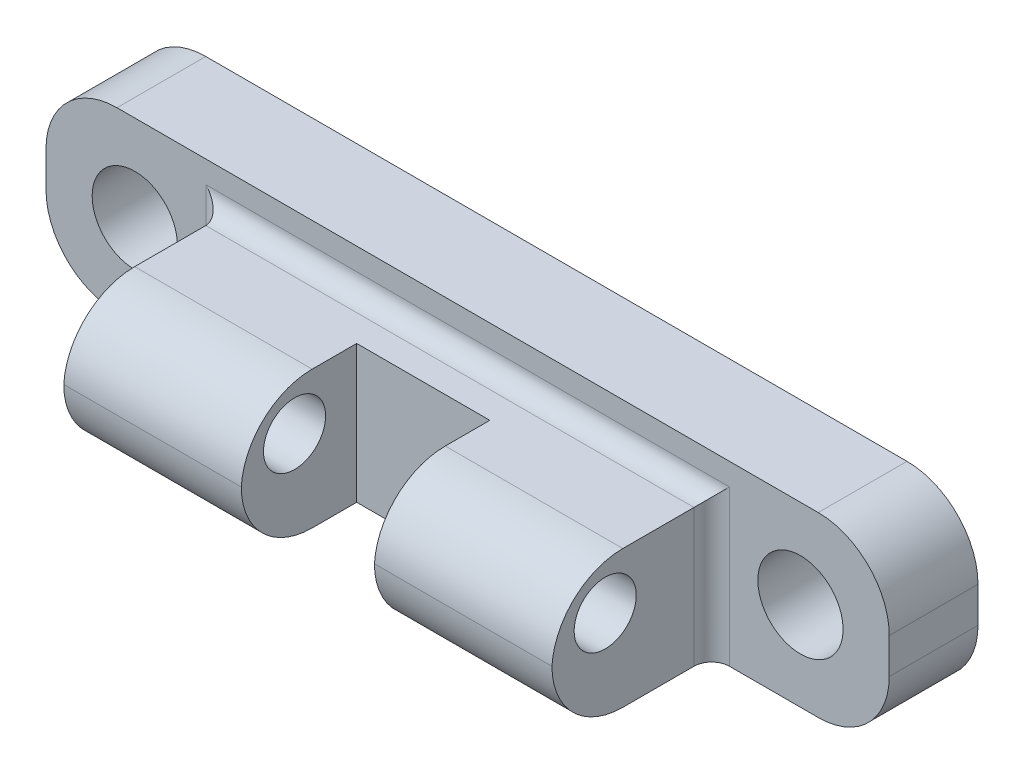
SolidWorks part; units mm, degrees
ref_plane "Front Plane" through (0, 0, 0) normal (0, 0, 1) x (1, 0, 0)
ref_plane "Top Plane" through (0, 0, 0) normal (0, 1, 0) x (1, 0, 0)
ref_plane "Right Plane" through (0, 0, 0) normal (1, 0, 0) x (0, 0, -1)
sketch "Sketch1" plane through (0, 0, 0) normal (0, 1, 0) x (1, 0, 0)
  line L3 (27.5, -2.7064) -> (17.5, -2.7064)
  line L4 (17.5, -2.7064) -> (17.5, 3.7936)
  line L5 (17.5, 3.7936) -> (10, 3.7936)
  line L6 (10, 3.7936) -> (10, -2.7064)
  line L7 (10, -2.7064) -> (0, -2.7064)
  line L8 (0, -2.7064) -> (0, 0)
  line L14 (-10, 11.2936) -> (-10, 6.2936)
  line L15 (-10, 6.2936) -> (0, 6.2936)
  line L16 (0, 6.2936) -> (0, -2.7064)
  line L17 (-10, 11.2936) -> (37.5, 11.2936)
  line L18 (27.5, -2.7064) -> (27.5, 6.2936)
  line L19 (27.5, 6.2936) -> (37.5, 6.2936)
  line L20 (37.5, 6.2936) -> (37.5, 11.2936)
  dimension "D1" = 7.5
  dimension "D2" = 10
  dimension "D3" = 10
  dimension "D4" = 6.5
  dimension "D5" = 6.5
  dimension "D6" = 14
  dimension "D7" = 10
  dimension "D8" = 10
  dimension "D9" = 5
  dimension "D10" = 5
extrude "Boss-Extrude1" add sketch "Sketch1" along normal blind 10 contours L19 L20 L17 L14 L15 L16 L8 L7 L6 L5 L4 L3 L18 region at (13.75, 0, -5.7441)
sketch "Sketch2" plane through (17.5, 0, 0) normal (-1, 0, 0) x (0, 0, 1)
  line L0 (2.7064, 10) -> (2.7064, 0) construction
  circle A0 centre (-0.2936, 5.0969) radius 1.75
  dimension "D1" = 3.5
  dimension "D2" = 3
extrude "Cut-Extrude1" cut sketch "Sketch2" against normal mid plane 60
sketch "Sketch3" plane through (0, 0, -6.2936) normal (0, 0, 1) x (1, 0, 0)
  line L0 (-10, 10) -> (0, 10) construction
  line L1 (27.5, 10) -> (37.5, 10) construction
  line L2 (0, 10) -> (0, 0) construction
  line L3 (37.5, 10) -> (37.5, 0) construction
  circle A0 centre (-5, 5) radius 2.4
  circle A1 centre (32.5, 5) radius 2.4
  dimension "D1" = 4.8
  dimension "D2" = 4.8
  dimension "D3" = 5
  dimension "D4" = 5
  dimension "D5" = 5
  dimension "D6" = 5
extrude "Cut-Extrude2" cut sketch "Sketch3" against normal mid plane 31
fillet "Fillet2" radius 4 2 edges at (5, 0, 2.7064) (22.5, 0, 2.7064)
fillet "Fillet3" radius 4 4 edges at (-10, 0, -8.7936) (-10, 10, -8.7936) (37.5, 0, -8.7936) (37.5, 10, -8.7936)
sketch "Sketch5" plane through (27.5, 0, 0) normal (1, 0, 0) x (0, 0, -1)
  line L0 (6.2936, 10) -> (6.2936, 6) construction
  line L1 (-2.7064, 10) -> (6.2936, 10)
  line L2 (-2.7064, 10) -> (-2.7064, 7.75)
  line L3 (-2.7064, 7.75) -> (6.2936, 7.75)
  line L4 (6.2936, 10) -> (6.2936, 7.75)
  dimension "D1" = 2.25
extrude "Cut-Extrude3" cut sketch "Sketch5" against normal mid plane 66
fillet "Fillet4" radius 4 2 edges at (22.5, 7.75, 2.7064) (5, 7.75, 2.7064)
fillet "Fillet5" radius 1 3 edges at (13.75, 7.75, -6.2936) (0, 3.875, -6.2936) (27.5, 3.875, -6.2936)
